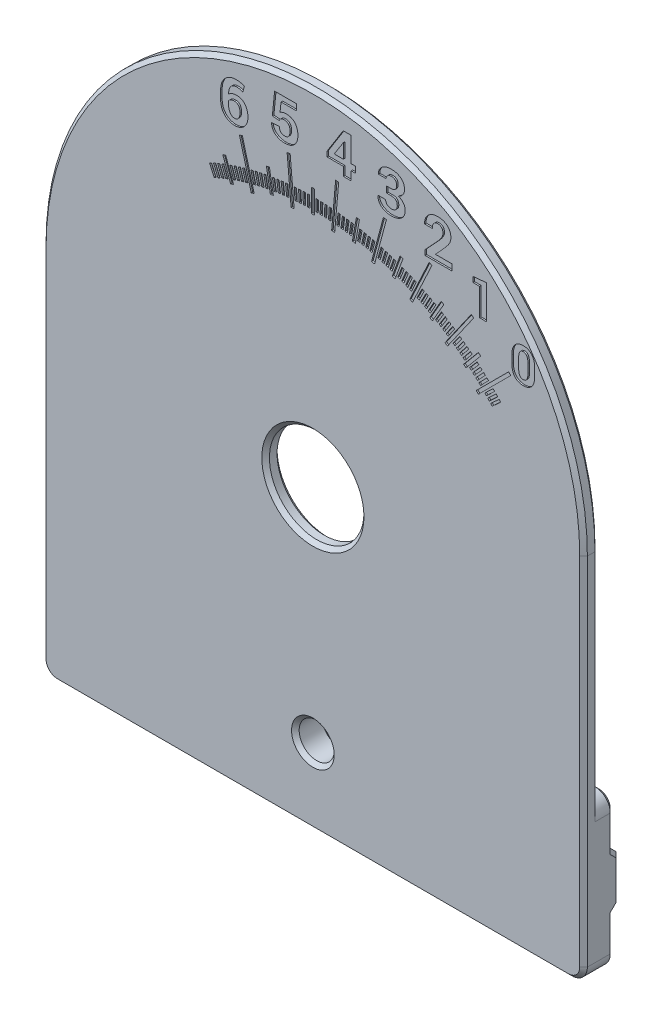
SolidWorks part; units mm, degrees
ref_plane "Front" through (0, 0, 0) normal (0, 0, 1) x (1, 0, 0)
ref_plane "Top" through (0, 0, 0) normal (0, 1, 0) x (1, 0, 0)
ref_plane "Right" through (0, 0, 0) normal (1, 0, 0) x (0, 0, -1)
sketch "Skizze1" plane through (0, 0, 0) normal (0, 0, 1) x (1, 0, 0)
  line L0 (0, 0) -> (35.5, 0)
  line L1 (0, 0) -> (0, 30.7358) construction
  line L2 (35.5, 5.5) -> (35.5, 0) construction
  line L3 (35.5, 0) -> (35.5, 28.6879)
  line L4 (-35.5, 0) -> (-35.5, 28.6879)
  line L5 (35.5, 0) -> (35.5, -20)
  line L6 (35.5, -20) -> (-35.5, -20)
  line L7 (-35.5, -20) -> (-35.5, 0)
  line L8 (-35.5, 0) -> (0, 0)
  arc A1 (35.5, 28.6879) -> (0, 64.1879) centre (0, 28.6879) ccw
  arc A2 (-35.5, 28.6879) -> (0, 64.1879) centre (0, 28.6879) cw
  dimension "D1" = 20
extrude "Aufsatz-Linear austragen1" add sketch "Skizze1" along normal blind 2 contours A2 L4 L8 L0 L3 A1 region at (0, 28.8397, 0)
sketch "Skizze2" plane through (0, 0, 2) normal (0, 0, 1) x (1, 0, 0)
  line L0 (0, 19) -> (0, 51.4601) construction
  line L1 (0, 19) -> (13.7352, 32.7352) construction
  line L2 (0, 19) -> (3.1812, 55.3611) construction
  line L3 (2.8575, 49.3665) -> (3.3804, 55.3437)
  line L4 (2.8575, 49.3665) -> (2.459, 49.4014)
  line L5 (3.3804, 55.3437) -> (3.1812, 55.3611)
  line L6 (2.9819, 55.3785) -> (3.1812, 55.3611)
  line L7 (2.459, 49.4014) -> (2.9819, 55.3785)
  line L8 (0, 19) -> (-2.3131, -14.0789) construction
  line L9 (2.3019, 51.9193) -> (2.4516, 51.9088)
  line L10 (2.4516, 51.9088) -> (2.3469, 50.4124)
  line L11 (2.3469, 50.4124) -> (2.0477, 50.4334)
  line L12 (2.1523, 51.9297) -> (2.0477, 50.4334)
  line L13 (2.3019, 51.9193) -> (2.1523, 51.9297)
  line L14 (0, 19) -> (-1.6664, -8.2459) construction
  line L15 (0, 19) -> (-1.7354, -14.1142) construction
  line L16 (1.5773, 51.9623) -> (1.4988, 50.4643)
  line L17 (1.7271, 51.9544) -> (1.5773, 51.9623)
  line L18 (1.7271, 51.9544) -> (1.8769, 51.9466)
  line L19 (1.8769, 51.9466) -> (1.7984, 50.4486)
  line L20 (1.4988, 50.4643) -> (1.7984, 50.4486)
  line L21 (0, 19) -> (-1.1573, -14.1395) construction
  line L22 (1.0018, 51.9848) -> (0.9494, 50.4857)
  line L23 (1.1517, 51.9795) -> (1.0018, 51.9848)
  line L24 (1.1517, 51.9795) -> (1.3016, 51.9743)
  line L25 (1.3016, 51.9743) -> (1.2492, 50.4752)
  line L26 (0.9494, 50.4857) -> (1.2492, 50.4752)
  line L27 (0, 19) -> (0, -14.1597) construction
  line L28 (0, 19) -> (-0.5787, -14.1546) construction
  line L34 (0.5759, 51.9946) -> (0.7259, 51.992)
  line L35 (0.5759, 51.9946) -> (0.4259, 51.9972)
  line L36 (0.4259, 51.9972) -> (0.3998, 50.4975)
  line L37 (0.6997, 50.4922) -> (0.3998, 50.4975)
  line L38 (0.7259, 51.992) -> (0.6997, 50.4922)
  line L39 (0, 53) -> (0.2, 53)
  line L40 (0.2, 53) -> (0.2, 50)
  line L41 (0.2, 50) -> (-0.2, 50)
  line L42 (-0.2, 53) -> (-0.2, 50)
  line L43 (0, 53) -> (-0.2, 53)
  line L44 (-2.4516, 51.9088) -> (-2.3469, 50.4124)
  line L45 (-2.3019, 51.9193) -> (-2.4516, 51.9088)
  line L46 (-2.3019, 51.9193) -> (-2.1523, 51.9297)
  line L47 (-2.1523, 51.9297) -> (-2.0477, 50.4334)
  line L48 (-2.3469, 50.4124) -> (-2.0477, 50.4334)
  line L49 (-1.7271, 51.9544) -> (-1.5773, 51.9623)
  line L50 (-1.7271, 51.9544) -> (-1.8769, 51.9466)
  line L51 (-1.8769, 51.9466) -> (-1.7984, 50.4486)
  line L52 (-1.4988, 50.4643) -> (-1.7984, 50.4486)
  line L53 (-1.5773, 51.9623) -> (-1.4988, 50.4643)
  line L54 (-1.1517, 51.9795) -> (-1.0018, 51.9848)
  line L55 (-1.1517, 51.9795) -> (-1.3016, 51.9743)
  line L56 (-1.3016, 51.9743) -> (-1.2492, 50.4752)
  line L57 (-0.9494, 50.4857) -> (-1.2492, 50.4752)
  line L58 (-1.0018, 51.9848) -> (-0.9494, 50.4857)
  line L59 (-0.5759, 51.9946) -> (-0.4259, 51.9972)
  line L60 (-0.4259, 51.9972) -> (-0.3998, 50.4975)
  line L61 (-0.6997, 50.4922) -> (-0.3998, 50.4975)
  line L62 (-0.7259, 51.992) -> (-0.6997, 50.4922)
  line L63 (-0.5759, 51.9946) -> (-0.7259, 51.992)
  line L64 (-2.459, 49.4014) -> (-2.9819, 55.3785)
  line L65 (-2.8575, 49.3665) -> (-2.459, 49.4014)
  line L66 (-2.8575, 49.3665) -> (-3.3804, 55.3437)
  line L67 (-3.3804, 55.3437) -> (-3.1812, 55.3611)
  line L68 (-2.9819, 55.3785) -> (-3.1812, 55.3611)
  line L69 (0, 19) -> (-3.1812, 55.3611) construction
  line L70 (-5.1623, 51.5934) -> (-5.0141, 51.6168)
  line L71 (-5.0141, 51.6168) -> (-4.7795, 50.1353)
  line L72 (-4.7795, 50.1353) -> (-5.0758, 50.0884)
  line L73 (-5.3104, 51.5699) -> (-5.0758, 50.0884)
  line L74 (-5.1623, 51.5934) -> (-5.3104, 51.5699)
  line L75 (-4.5927, 51.6785) -> (-4.4441, 51.6994)
  line L76 (-4.4441, 51.6994) -> (-4.2354, 50.214)
  line L77 (-4.5324, 50.1722) -> (-4.2354, 50.214)
  line L78 (-4.7412, 51.6576) -> (-4.5324, 50.1722)
  line L79 (-4.5927, 51.6785) -> (-4.7412, 51.6576)
  line L80 (-4.0216, 51.7537) -> (-3.8728, 51.7719)
  line L81 (-3.8728, 51.7719) -> (-3.69, 50.2831)
  line L82 (-3.9877, 50.2466) -> (-3.69, 50.2831)
  line L83 (-4.1705, 51.7354) -> (-3.9877, 50.2466)
  line L84 (-4.0216, 51.7537) -> (-4.1705, 51.7354)
  line L85 (-3.4494, 51.8189) -> (-3.3002, 51.8345)
  line L86 (-3.4494, 51.8189) -> (-3.5986, 51.8032)
  line L87 (-3.5986, 51.8032) -> (-3.4418, 50.3114)
  line L88 (-3.1434, 50.3428) -> (-3.4418, 50.3114)
  line L89 (-3.3002, 51.8345) -> (-3.1434, 50.3428)
  line L90 (-6.101, 52.4487) -> (-5.5801, 49.4943)
  line L91 (-5.904, 52.4835) -> (-6.101, 52.4487)
  line L92 (-5.904, 52.4835) -> (-5.7071, 52.5182)
  line L93 (-5.7071, 52.5182) -> (-5.1861, 49.5638)
  line L94 (-5.5801, 49.4943) -> (-5.1861, 49.5638)
  line L95 (0, 19) -> (-5.6366, 50.967) construction
  line L96 (0, 19) -> (-9.4469, 54.2563) construction
  line L97 (-7.7008, 48.5125) -> (-8.0872, 48.409)
  line L98 (-7.7008, 48.5125) -> (-9.2537, 54.3081)
  line L99 (-9.2537, 54.3081) -> (-9.4469, 54.2563)
  line L100 (-9.6401, 54.2045) -> (-9.4469, 54.2563)
  line L101 (-8.0872, 48.409) -> (-9.6401, 54.2045)
  line L102 (-7.9833, 51.0194) -> (-7.8378, 51.0557)
  line L103 (-7.8378, 51.0557) -> (-7.4749, 49.6003)
  line L104 (-7.766, 49.5277) -> (-7.4749, 49.6003)
  line L105 (-8.1289, 50.9831) -> (-7.766, 49.5277)
  line L106 (-7.9833, 51.0194) -> (-8.1289, 50.9831)
  line L107 (-7.4233, 51.1539) -> (-7.2771, 51.1876)
  line L108 (-7.2771, 51.1876) -> (-6.9397, 49.7261)
  line L109 (-6.9397, 49.7261) -> (-7.232, 49.6586)
  line L110 (-7.5695, 51.1201) -> (-7.232, 49.6586)
  line L111 (-7.4233, 51.1539) -> (-7.5695, 51.1201)
  line L112 (-6.861, 51.2785) -> (-6.7143, 51.3097)
  line L113 (-6.7143, 51.3097) -> (-6.4024, 49.8425)
  line L114 (-6.4024, 49.8425) -> (-6.6959, 49.7801)
  line L115 (-7.0077, 51.2473) -> (-6.6959, 49.7801)
  line L116 (-6.861, 51.2785) -> (-7.0077, 51.2473)
  line L117 (-6.2966, 51.3933) -> (-6.1494, 51.422)
  line L118 (-6.1494, 51.422) -> (-5.8632, 49.9495)
  line L119 (-6.1577, 49.8923) -> (-5.8632, 49.9495)
  line L120 (-6.4439, 51.3647) -> (-6.1577, 49.8923)
  line L121 (-6.2966, 51.3933) -> (-6.4439, 51.3647)
  line L122 (0, 19) -> (-11.102, 49.5026) construction
  line L123 (-11.6287, 50.9495) -> (-11.4407, 51.018)
  line L124 (-11.6287, 50.9495) -> (-11.8166, 50.8811)
  line L125 (-11.8166, 50.8811) -> (-10.7906, 48.0621)
  line L126 (-10.4147, 48.1989) -> (-10.7906, 48.0621)
  line L127 (-11.4407, 51.018) -> (-10.4147, 48.1989)
  line L128 (-10.7436, 50.2018) -> (-10.6018, 50.2506)
  line L129 (-10.6018, 50.2506) -> (-10.1135, 48.8323)
  line L130 (-10.1135, 48.8323) -> (-10.3971, 48.7347)
  line L131 (-10.8855, 50.1529) -> (-10.3971, 48.7347)
  line L132 (-10.7436, 50.2018) -> (-10.8855, 50.1529)
  line L133 (-10.1975, 50.3845) -> (-10.0548, 50.4309)
  line L134 (-10.0548, 50.4309) -> (-9.5913, 49.0043)
  line L135 (-9.8766, 48.9116) -> (-9.5913, 49.0043)
  line L136 (-10.3401, 50.3382) -> (-9.8766, 48.9116)
  line L137 (-10.1975, 50.3845) -> (-10.3401, 50.3382)
  line L138 (-9.6482, 50.5577) -> (-9.5047, 50.6016)
  line L139 (-9.5047, 50.6016) -> (-9.0662, 49.1671)
  line L140 (-9.353, 49.0794) -> (-9.0662, 49.1671)
  line L141 (-9.7916, 50.5139) -> (-9.353, 49.0794)
  line L142 (-9.6482, 50.5577) -> (-9.7916, 50.5139)
  line L143 (-9.0959, 50.7213) -> (-8.9517, 50.7626)
  line L144 (-8.9517, 50.7626) -> (-8.5383, 49.3207)
  line L145 (-8.5383, 49.3207) -> (-8.8267, 49.2381)
  line L146 (-9.2401, 50.6799) -> (-8.8267, 49.2381)
  line L147 (-9.0959, 50.7213) -> (-9.2401, 50.6799)
  line L148 (-13.4222, 49.1467) -> (-13.2851, 49.2077)
  line L149 (-13.2851, 49.2077) -> (-12.675, 47.8374)
  line L150 (-12.9491, 47.7153) -> (-12.675, 47.8374)
  line L151 (-13.5592, 49.0857) -> (-12.9491, 47.7153)
  line L152 (-13.4222, 49.1467) -> (-13.5592, 49.0857)
  line L153 (-12.894, 49.3763) -> (-12.7559, 49.4349)
  line L154 (-12.7559, 49.4349) -> (-12.1698, 48.0542)
  line L155 (-12.1698, 48.0542) -> (-12.446, 47.937)
  line L156 (-13.0321, 49.3177) -> (-12.446, 47.937)
  line L157 (-12.894, 49.3763) -> (-13.0321, 49.3177)
  line L158 (-12.3619, 49.5967) -> (-12.2228, 49.6529)
  line L159 (-12.2228, 49.6529) -> (-11.6609, 48.2622)
  line L160 (-11.6609, 48.2622) -> (-11.9391, 48.1498)
  line L161 (-12.501, 49.5405) -> (-11.9391, 48.1498)
  line L162 (-12.3619, 49.5967) -> (-12.501, 49.5405)
  line L163 (-11.826, 49.8078) -> (-11.686, 49.8616)
  line L164 (-11.686, 49.8616) -> (-11.1484, 48.4612)
  line L165 (-11.4285, 48.3537) -> (-11.1484, 48.4612)
  line L166 (-11.9661, 49.7541) -> (-11.4285, 48.3537)
  line L167 (-11.826, 49.8078) -> (-11.9661, 49.7541)
  line L168 (3.3002, 51.8345) -> (3.1434, 50.3428)
  line L169 (3.4494, 51.8189) -> (3.3002, 51.8345)
  line L170 (3.4494, 51.8189) -> (3.5986, 51.8032)
  line L171 (3.5986, 51.8032) -> (3.4418, 50.3114)
  line L172 (3.1434, 50.3428) -> (3.4418, 50.3114)
  line L173 (4.0216, 51.7537) -> (4.1705, 51.7354)
  line L174 (4.0216, 51.7537) -> (3.8728, 51.7719)
  line L175 (3.8728, 51.7719) -> (3.69, 50.2831)
  line L176 (3.9877, 50.2466) -> (3.69, 50.2831)
  line L177 (4.1705, 51.7354) -> (3.9877, 50.2466)
  line L178 (4.5927, 51.6785) -> (4.7412, 51.6576)
  line L179 (4.5927, 51.6785) -> (4.4441, 51.6994)
  line L180 (4.4441, 51.6994) -> (4.2354, 50.214)
  line L181 (4.5324, 50.1722) -> (4.2354, 50.214)
  line L182 (4.7412, 51.6576) -> (4.5324, 50.1722)
  line L183 (5.1623, 51.5934) -> (5.3104, 51.5699)
  line L184 (5.3104, 51.5699) -> (5.0758, 50.0884)
  line L185 (4.7795, 50.1353) -> (5.0758, 50.0884)
  line L186 (5.0141, 51.6168) -> (4.7795, 50.1353)
  line L187 (5.1623, 51.5934) -> (5.0141, 51.6168)
  line L188 (0, 19) -> (5.6366, 50.967) construction
  line L189 (5.7071, 52.5182) -> (5.1861, 49.5638)
  line L190 (5.904, 52.4835) -> (5.7071, 52.5182)
  line L191 (5.904, 52.4835) -> (6.101, 52.4487)
  line L192 (6.101, 52.4487) -> (5.5801, 49.4943)
  line L193 (5.1861, 49.5638) -> (5.5801, 49.4943)
  line L194 (6.2966, 51.3933) -> (6.4439, 51.3647)
  line L195 (6.4439, 51.3647) -> (6.1577, 49.8923)
  line L196 (6.1577, 49.8923) -> (5.8632, 49.9495)
  line L197 (6.1494, 51.422) -> (5.8632, 49.9495)
  line L198 (6.2966, 51.3933) -> (6.1494, 51.422)
  line L199 (6.861, 51.2785) -> (7.0077, 51.2473)
  line L200 (7.0077, 51.2473) -> (6.6959, 49.7801)
  line L201 (6.4024, 49.8425) -> (6.6959, 49.7801)
  line L202 (6.7143, 51.3097) -> (6.4024, 49.8425)
  line L203 (6.861, 51.2785) -> (6.7143, 51.3097)
  line L204 (7.4233, 51.1539) -> (7.5695, 51.1201)
  line L205 (7.5695, 51.1201) -> (7.232, 49.6586)
  line L206 (6.9397, 49.7261) -> (7.232, 49.6586)
  line L207 (7.2771, 51.1876) -> (6.9397, 49.7261)
  line L208 (7.4233, 51.1539) -> (7.2771, 51.1876)
  line L209 (7.9833, 51.0194) -> (8.1289, 50.9831)
  line L210 (7.9833, 51.0194) -> (7.8378, 51.0557)
  line L211 (7.8378, 51.0557) -> (7.4749, 49.6003)
  line L212 (7.766, 49.5277) -> (7.4749, 49.6003)
  line L213 (8.1289, 50.9831) -> (7.766, 49.5277)
  line L214 (0, 19) -> (9.4469, 54.2563) construction
  line L215 (8.0872, 48.409) -> (9.6401, 54.2045)
  line L216 (7.7008, 48.5125) -> (8.0872, 48.409)
  line L217 (7.7008, 48.5125) -> (9.2537, 54.3081)
  line L218 (9.2537, 54.3081) -> (9.4469, 54.2563)
  line L219 (9.6401, 54.2045) -> (9.4469, 54.2563)
  line L220 (9.0959, 50.7213) -> (9.2401, 50.6799)
  line L221 (9.2401, 50.6799) -> (8.8267, 49.2381)
  line L222 (8.5383, 49.3207) -> (8.8267, 49.2381)
  line L223 (8.9517, 50.7626) -> (8.5383, 49.3207)
  line L224 (9.0959, 50.7213) -> (8.9517, 50.7626)
  line L225 (9.6482, 50.5577) -> (9.7916, 50.5139)
  line L226 (9.7916, 50.5139) -> (9.353, 49.0794)
  line L227 (9.353, 49.0794) -> (9.0662, 49.1671)
  line L228 (9.5047, 50.6016) -> (9.0662, 49.1671)
  line L229 (9.6482, 50.5577) -> (9.5047, 50.6016)
  line L230 (10.1975, 50.3845) -> (10.3401, 50.3382)
  line L231 (10.3401, 50.3382) -> (9.8766, 48.9116)
  line L232 (9.8766, 48.9116) -> (9.5913, 49.0043)
  line L233 (10.0548, 50.4309) -> (9.5913, 49.0043)
  line L234 (10.1975, 50.3845) -> (10.0548, 50.4309)
  line L235 (10.7436, 50.2018) -> (10.8855, 50.1529)
  line L236 (10.8855, 50.1529) -> (10.3971, 48.7347)
  line L237 (10.1135, 48.8323) -> (10.3971, 48.7347)
  line L238 (10.6018, 50.2506) -> (10.1135, 48.8323)
  line L239 (10.7436, 50.2018) -> (10.6018, 50.2506)
  line L240 (0, 19) -> (11.102, 49.5026) construction
  line L241 (11.6287, 50.9495) -> (11.8166, 50.8811)
  line L242 (11.6287, 50.9495) -> (11.4407, 51.018)
  line L243 (11.4407, 51.018) -> (10.4147, 48.1989)
  line L244 (10.7906, 48.0621) -> (10.4147, 48.1989)
  line L245 (11.8166, 50.8811) -> (10.7906, 48.0621)
  line L246 (11.826, 49.8078) -> (11.9661, 49.7541)
  line L247 (11.9661, 49.7541) -> (11.4285, 48.3537)
  line L248 (11.4285, 48.3537) -> (11.1484, 48.4612)
  line L249 (11.686, 49.8616) -> (11.1484, 48.4612)
  line L250 (11.826, 49.8078) -> (11.686, 49.8616)
  line L251 (12.3619, 49.5967) -> (12.501, 49.5405)
  line L252 (12.501, 49.5405) -> (11.9391, 48.1498)
  line L253 (11.6609, 48.2622) -> (11.9391, 48.1498)
  line L254 (12.2228, 49.6529) -> (11.6609, 48.2622)
  line L255 (12.3619, 49.5967) -> (12.2228, 49.6529)
  line L256 (12.894, 49.3763) -> (13.0321, 49.3177)
  line L257 (13.0321, 49.3177) -> (12.446, 47.937)
  line L258 (12.1698, 48.0542) -> (12.446, 47.937)
  line L259 (12.7559, 49.4349) -> (12.1698, 48.0542)
  line L260 (12.894, 49.3763) -> (12.7559, 49.4349)
  line L261 (13.4222, 49.1467) -> (13.5592, 49.0857)
  line L262 (13.5592, 49.0857) -> (12.9491, 47.7153)
  line L263 (12.9491, 47.7153) -> (12.675, 47.8374)
  line L264 (13.2851, 49.2077) -> (12.675, 47.8374)
  line L265 (13.4222, 49.1467) -> (13.2851, 49.2077)
  line L266 (0, 19) -> (15.4256, 52.0802) construction
  line L267 (13.0711, 46.5579) -> (12.7086, 46.7269)
  line L268 (13.0711, 46.5579) -> (15.6068, 51.9957)
  line L269 (15.6068, 51.9957) -> (15.4256, 52.0802)
  line L270 (15.2443, 52.1648) -> (15.4256, 52.0802)
  line L271 (12.7086, 46.7269) -> (15.2443, 52.1648)
  line L272 (21.8548, 45.0455) -> (22.008, 44.917)
  line L273 (21.8548, 45.0455) -> (21.7016, 45.1741)
  line L274 (21.7016, 45.1741) -> (19.7732, 42.8759)
  line L275 (20.0796, 42.6188) -> (19.7732, 42.8759)
  line L276 (22.008, 44.917) -> (20.0796, 42.6188)
  line L277 (20.7673, 44.6455) -> (20.8839, 44.5511)
  line L278 (20.8839, 44.5511) -> (19.9399, 43.3854)
  line L279 (19.7068, 43.5742) -> (19.9399, 43.3854)
  line L280 (20.6508, 44.7399) -> (19.7068, 43.5742)
  line L281 (20.7673, 44.6455) -> (20.6508, 44.7399)
  line L282 (20.3166, 45.0041) -> (20.4348, 44.9117)
  line L283 (20.4348, 44.9117) -> (19.5113, 43.7297)
  line L284 (19.5113, 43.7297) -> (19.2749, 43.9144)
  line L285 (20.1984, 45.0964) -> (19.2749, 43.9144)
  line L286 (20.3166, 45.0041) -> (20.1984, 45.0964)
  line L287 (19.8597, 45.3547) -> (19.9795, 45.2644)
  line L288 (19.9795, 45.2644) -> (19.0768, 44.0665)
  line L289 (19.0768, 44.0665) -> (18.8372, 44.247)
  line L290 (19.7399, 45.445) -> (18.8372, 44.247)
  line L291 (19.8597, 45.3547) -> (19.7399, 45.445)
  line L292 (19.3967, 45.6973) -> (19.5181, 45.6091)
  line L293 (19.5181, 45.6091) -> (18.6364, 44.3956)
  line L294 (18.3937, 44.5719) -> (18.6364, 44.3956)
  line L295 (19.2754, 45.7854) -> (18.3937, 44.5719)
  line L296 (19.3967, 45.6973) -> (19.2754, 45.7854)
  line L297 (17.6579, 43.8694) -> (17.3303, 44.0989)
  line L298 (17.6579, 43.8694) -> (21.0994, 48.7843)
  line L299 (21.0994, 48.7843) -> (20.9355, 48.899)
  line L300 (20.7717, 49.0138) -> (20.9355, 48.899)
  line L301 (17.3303, 44.0989) -> (20.7717, 49.0138)
  line L302 (18.4532, 46.3579) -> (18.5775, 46.2741)
  line L303 (18.5775, 46.2741) -> (17.7387, 45.0305)
  line L304 (17.7387, 45.0305) -> (17.49, 45.1983)
  line L305 (18.3288, 46.4418) -> (17.49, 45.1983)
  line L306 (18.4532, 46.3579) -> (18.3288, 46.4418)
  line L307 (17.9729, 46.6758) -> (18.0987, 46.5941)
  line L308 (18.0987, 46.5941) -> (17.2817, 45.3361)
  line L309 (17.0301, 45.4995) -> (17.2817, 45.3361)
  line L310 (17.8471, 46.7575) -> (17.0301, 45.4995)
  line L311 (17.9729, 46.6758) -> (17.8471, 46.7575)
  line L312 (17.4871, 46.9853) -> (17.6144, 46.9058)
  line L313 (17.6144, 46.9058) -> (16.8195, 45.6337)
  line L314 (16.5651, 45.7927) -> (16.8195, 45.6337)
  line L315 (17.3599, 47.0648) -> (16.5651, 45.7927)
  line L316 (17.4871, 46.9853) -> (17.3599, 47.0648)
  line L317 (16.9961, 47.2862) -> (17.1246, 47.209)
  line L318 (17.1246, 47.209) -> (16.3521, 45.9232)
  line L319 (16.3521, 45.9232) -> (16.0949, 46.0777)
  line L320 (16.8675, 47.3635) -> (16.0949, 46.0777)
  line L321 (16.9961, 47.2862) -> (16.8675, 47.3635)
  line L322 (17, 48.4449) -> (17.1732, 48.3449)
  line L323 (17.1732, 48.3449) -> (15.6732, 45.7468)
  line L324 (15.3268, 45.9468) -> (15.6732, 45.7468)
  line L325 (16.8268, 48.5449) -> (15.3268, 45.9468)
  line L326 (17, 48.4449) -> (16.8268, 48.5449)
  line L327 (15.9985, 47.8621) -> (16.1297, 47.7894)
  line L328 (16.1297, 47.7894) -> (15.4025, 46.4775)
  line L329 (15.1401, 46.6229) -> (15.4025, 46.4775)
  line L330 (15.8674, 47.9349) -> (15.1401, 46.6229)
  line L331 (15.9985, 47.8621) -> (15.8674, 47.9349)
  line L332 (15.4924, 48.137) -> (15.6248, 48.0665)
  line L333 (15.6248, 48.0665) -> (14.9206, 46.7421)
  line L334 (14.9206, 46.7421) -> (14.6557, 46.883)
  line L335 (15.36, 48.2074) -> (14.6557, 46.883)
  line L336 (15.4924, 48.137) -> (15.36, 48.2074)
  line L337 (14.9815, 48.4029) -> (15.1152, 48.3348)
  line L338 (15.1152, 48.3348) -> (14.4342, 46.9983)
  line L339 (14.4342, 46.9983) -> (14.1669, 47.1345)
  line L340 (14.8479, 48.471) -> (14.1669, 47.1345)
  line L341 (14.9815, 48.4029) -> (14.8479, 48.471)
  line L342 (14.4661, 48.6599) -> (14.6009, 48.5941)
  line L343 (14.6009, 48.5941) -> (13.9434, 47.2459)
  line L344 (13.6737, 47.3774) -> (13.9434, 47.2459)
  line L345 (14.3313, 48.7256) -> (13.6737, 47.3774)
  line L346 (14.4661, 48.6599) -> (14.3313, 48.7256)
  line L347 (0, 19) -> (20.865, 43.8659) construction
  line L348 (24.5235, 41.0811) -> (24.6239, 40.9696)
  line L349 (24.6239, 40.9696) -> (23.5092, 39.9659)
  line L350 (23.5092, 39.9659) -> (23.3084, 40.1888)
  line L351 (24.4231, 41.1925) -> (23.3084, 40.1888)
  line L352 (24.5235, 41.0811) -> (24.4231, 41.1925)
  line L353 (24.1344, 41.5057) -> (24.2367, 41.396)
  line L354 (24.2367, 41.396) -> (23.1397, 40.373)
  line L355 (23.1397, 40.373) -> (22.9351, 40.5924)
  line L356 (24.0321, 41.6154) -> (22.9351, 40.5924)
  line L357 (24.1344, 41.5057) -> (24.0321, 41.6154)
  line L358 (23.738, 41.9235) -> (23.8422, 41.8156)
  line L359 (23.8422, 41.8156) -> (22.7631, 40.7736)
  line L360 (22.5547, 40.9894) -> (22.7631, 40.7736)
  line L361 (23.6338, 42.0314) -> (22.5547, 40.9894)
  line L362 (23.738, 41.9235) -> (23.6338, 42.0314)
  line L363 (21.4253, 40.7082) -> (25.668, 44.9508)
  line L364 (25.668, 44.9508) -> (25.8094, 44.8094)
  line L365 (25.9508, 44.668) -> (25.8094, 44.8094)
  line L366 (21.7082, 40.4253) -> (25.9508, 44.668)
  line L367 (21.4253, 40.7082) -> (21.7082, 40.4253)
  line L368 (22.9235, 42.738) -> (23.0314, 42.6338)
  line L369 (23.0314, 42.6338) -> (21.9894, 41.5547)
  line L370 (21.9894, 41.5547) -> (21.7736, 41.7631)
  line L371 (22.8156, 42.8422) -> (21.7736, 41.7631)
  line L372 (22.9235, 42.738) -> (22.8156, 42.8422)
  line L373 (22.5057, 43.1344) -> (22.6154, 43.0321)
  line L374 (22.6154, 43.0321) -> (21.5924, 41.9351)
  line L375 (21.373, 42.1397) -> (21.5924, 41.9351)
  line L376 (22.396, 43.2367) -> (21.373, 42.1397)
  line L377 (22.5057, 43.1344) -> (22.396, 43.2367)
  line L378 (22.0811, 43.5235) -> (22.1925, 43.4231)
  line L379 (22.1925, 43.4231) -> (21.1888, 42.3084)
  line L380 (20.9659, 42.5092) -> (21.1888, 42.3084)
  line L381 (21.9696, 43.6239) -> (20.9659, 42.5092)
  line L382 (22.0811, 43.5235) -> (21.9696, 43.6239)
  line L383 (21.6497, 43.9051) -> (21.7629, 43.8067)
  line L384 (21.7629, 43.8067) -> (20.7788, 42.6747)
  line L385 (20.7788, 42.6747) -> (20.5524, 42.8715)
  line L386 (21.5365, 44.0036) -> (20.5524, 42.8715)
  line L387 (21.6497, 43.9051) -> (21.5365, 44.0036)
  circle A1 centre (0, 19) radius 31.5 construction
  point P7 (0, 50.5)
  point P14 (2.6583, 49.3839)
  point P22 (2.1973, 50.4229)
  point P39 (0, 50)
  point P392 (2.7454, 50.3801)
  dimension "D11" = 63
  dimension "D1" = 45
  dimension "D2" = 5
  dimension "D3" = 0.4
  dimension "D4" = 6
  dimension "D5" = 1
  dimension "D6" = 1.5
  dimension "D7" = 0.3
  dimension "D8" = 0.5
  dimension "D9" = 0.4
  dimension "D10" = 3
  dimension "D12" = 1
  dimension "D13" = 0.5
extrude "Schnitt-Linear austragen1" cut sketch "Skizze2" against normal blind 0.2
sketch "Skizze4" plane through (0, 0, 2) normal (0, 0, 1) x (1, 0, 0)
  circle A0 centre (0, 19) radius 6.2
  dimension "D1" = 12.4
extrude "Schnitt-Linear austragen2" cut sketch "Skizze4" against normal through all
sketch "Skizze3" plane through (0, 0, 2) normal (0, 0, 1) x (1, 0, 0)
  line L0 (0, 0) -> (0, 74.8793) construction
  line L3 (30.5937, 44.3937) -> (24.5937, 44.3937) construction
  line L4 (19.2468, 49.1883) -> (25.2468, 49.1883) construction
  line L5 (13.4601, 52.6944) -> (19.4601, 52.6944) construction
  line L6 (7.3695, 55.0378) -> (13.3695, 55.0378) construction
  line L7 (0.7176, 56.3153) -> (6.7176, 56.3153) construction
  line L8 (-7.3695, 55.0378) -> (-13.3695, 55.0378) construction
  line L9 (-0.7176, 56.3153) -> (-6.7176, 56.3153) construction
  circle A0 centre (0, 19) radius 37.5 construction
  text T0 "0" font "Roboto" height in points 12
  text T1 "1" font "Roboto" height in points 12
  text T2 "2" font "Roboto" height in points 14
  text T3 "3" font "Roboto" height in points 14
  text T4 "4" font "Roboto" height in points 14
  text T5 "5" font "Roboto" height in points 14
  text T6 "6" font "Roboto" height in points 14
  point P0 (0.37, 0)
  point P2 (0, -0.3468)
  point P4 (3.2941, 56.355)
  point P7 (35.8991, 29.8398)
  point P8 (27.5937, 44.3937)
  point P16 (22.2468, 49.1883)
  point P17 (16.4601, 52.6944)
  point P20 (10.3695, 55.0378)
  point P23 (3.7176, 56.3153)
  point P24 (9.643, 55.239)
  point P25 (16.0236, 52.9042)
  point P26 (22.2468, 49.1883)
  point P28 (28.2087, 43.7087)
  point P30 (16.4601, 52.6944)
  point P31 (9.6793, 54.1932)
  point P37 (7.093, 54.0768)
  point P38 (0.6185, 55.3202)
  point P39 (0, 0)
  dimension "D1" = 75
  dimension "D2" = 6
extrude "Schnitt-Linear austragen3" cut sketch "Skizze3" against normal blind 0.2
extrude "Aufsatz-Linear austragen2" add sketch "Skizze1<3>" along normal blind 2 and the other way blind 2 contours L8 L7 L6 L5 L0 region at (0, -10, 0)
sketch "Skizze1<3>" plane through (0, 0, 0) normal (0, 0, 1) x (1, 0, 0) same geometry as "Skizze1"
sketch "Skizze5" plane through (-35.5, 0, 0) normal (-1, 0, 0) x (0, 0, 1)
  line L0 (-2, -10) -> (-12.7757, -10) construction
  line L1 (-2, -20) -> (-2, 0) construction
  line L2 (-2, -13.5) -> (-2, -6.5)
  line L3 (-2, -6.5) -> (-2.75, -7.25)
  line L4 (-2.75, -7.25) -> (-2.75, -12.75)
  line L5 (-2, -13.5) -> (-2.75, -12.75)
  point P4 (-2.75, -7.2266)
  point P9 (-2.75, -10)
  dimension "D1" = 0.75
  dimension "D2" = 7
  dimension "D3" = 45
extrude "Aufsatz-Linear austragen3" add sketch "Skizze5" against normal up to surface (71 mm away) up to face at (35.5, 2.896, 0)
sketch "Skizze6" plane through (0, 0, 2) normal (0, 0, 1) x (1, 0, 0)
  line L0 (0, 0) -> (0, -20) construction
  line L1 (35.5, -20) -> (-35.5, -20) construction
  circle A0 centre (0, -10) radius 2.3
  dimension "D1" = 4.6
extrude "Schnitt-Linear austragen4" cut sketch "Skizze6" against normal through all
sketch "Skizze7" plane through (0, 0, -2) normal (0, 0, -1) x (-1, 0, 0)
  circle A0 centre (0, -10) radius 4.15
  dimension "D1" = 8.3
extrude "Schnitt-Linear austragen5" cut sketch "Skizze7" along normal blind 2
fillet "Verrundung1" radius 1 2 edges at (-4.15, -10, -2.75) (4.15, -10, -2.75)
fillet "Verrundung2" radius 2 4 edges at (35.5, -20, 0) (35.5, 0, -1) (-35.5, 0, -1) (-35.5, -20, 0)
chamfer "Fase1" distance 0.5 angle 45 29 edges at (-35.5, 13.344, 0) (35.5, 13.344, 0) (0, 64.1879, 0) (-2.3, -10, -2) (2.3, -10, 2) (6.2, 19, 2) (6.2, 19, 0) (0, 0, -2) (0, -20, -2) (35.5, 5.344, 2) (0, 64.1879, 2) (0, -20, 2) (-35.5, 5.344, 2) (35.5, -13.125, -2.375) (35.5, -10, -2.75) (35.5, -6.875, -2.375) (35.5, -4.25, -2) (34.9142, -0.5858, -2) (-34.9142, -0.5858, -2) (-35.5, -13.125, -2.375) (-35.5, -10, -2.75) (-35.5, -6.875, -2.375) (-35.5, -4.25, -2) (35.5, -15.75, -2) (-35.5, -15.75, -2) (34.9142, -19.4142, -2) (-34.9142, -19.4142, -2) (34.9142, -19.4142, 2) (-34.9142, -19.4142, 2)
